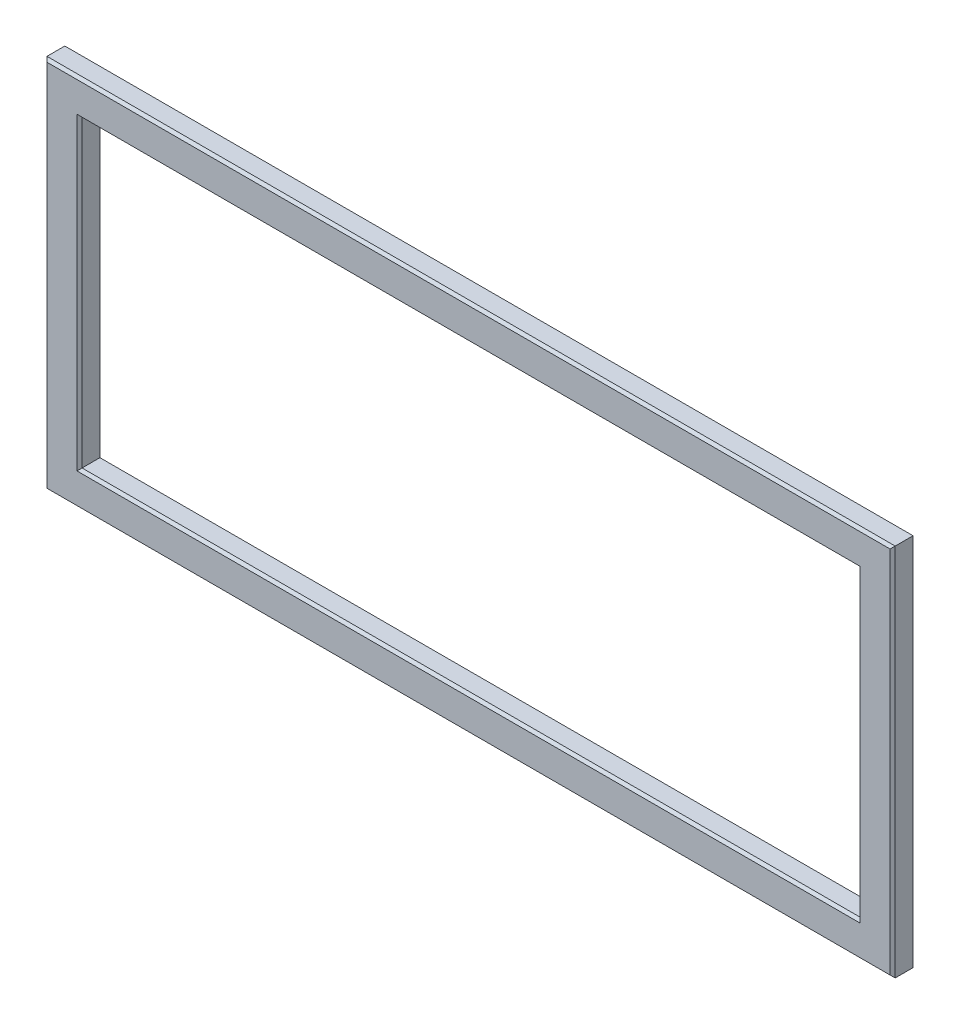
SolidWorks part; units mm, degrees
material "7075-T6 (SN)"
ref_plane "Front Plane" through (0, 0, 0) normal (0, 0, 1) x (1, 0, 0)
ref_plane "Top Plane" through (0, 0, 0) normal (0, 1, 0) x (1, 0, 0)
ref_plane "Right Plane" through (0, 0, 0) normal (1, 0, 0) x (0, 0, -1)
sketch "Sketch1" plane through (0, 0, 0) normal (0, 0, 1) x (1, 0, 0)
  line L43 (-4.2125, 142.325) -> (328.0625, 142.325)
  line L44 (-4.2125, 142.325) -> (-4.2125, -4.2125)
  line L45 (-4.2125, -4.2125) -> (328.0625, -4.2125)
  line L46 (328.0625, 142.325) -> (328.0625, -4.2125)
  line L104 (313.8, 130.5625) -> (292.3, 130.5625)
  line L105 (290.8, 132.0625) -> (290.8, 132.5625)
  line L106 (280.8, 132.5625) -> (280.8, 132.0625)
  line L107 (279.3, 130.5625) -> (168.425, 130.5625)
  line L108 (166.925, 132.0625) -> (166.925, 132.5625)
  line L109 (156.925, 132.5625) -> (156.925, 132.0625)
  line L110 (155.425, 130.5625) -> (44.55, 130.5625)
  line L111 (43.05, 132.0625) -> (43.05, 132.5625)
  line L112 (33.05, 132.5625) -> (33.05, 132.0625)
  line L113 (31.55, 130.5625) -> (10.05, 130.5625)
  line L114 (7.55, 128.0625) -> (7.55, 116.5625)
  line L115 (6.05, 115.0625) -> (5.55, 115.0625)
  line L116 (5.55, 105.0625) -> (6.05, 105.0625)
  line L117 (7.55, 103.5625) -> (7.55, 34.55)
  line L118 (6.05, 33.05) -> (5.55, 33.05)
  line L119 (5.55, 23.05) -> (6.05, 23.05)
  line L120 (7.55, 21.55) -> (7.55, 10.05)
  line L121 (10.05, 7.55) -> (31.55, 7.55)
  line L122 (33.05, 6.05) -> (33.05, 5.55)
  line L123 (43.05, 5.55) -> (43.05, 6.05)
  line L124 (44.55, 7.55) -> (155.425, 7.55)
  line L125 (156.925, 6.05) -> (156.925, 5.55)
  line L126 (166.925, 5.55) -> (166.925, 6.05)
  line L127 (168.425, 7.55) -> (279.3, 7.55)
  line L128 (280.8, 6.05) -> (280.8, 5.55)
  line L129 (290.8, 5.55) -> (290.8, 6.05)
  line L130 (292.3, 7.55) -> (313.8, 7.55)
  line L131 (316.3, 10.05) -> (316.3, 21.55)
  line L132 (317.8, 23.05) -> (318.3, 23.05)
  line L133 (318.3, 33.05) -> (317.8, 33.05)
  line L134 (316.3, 34.55) -> (316.3, 103.5625)
  line L135 (317.8, 105.0625) -> (318.3, 105.0625)
  line L136 (318.3, 115.0625) -> (317.8, 115.0625)
  line L137 (316.3, 116.5625) -> (316.3, 128.0625)
  line L138 (313.8, 130.5625) -> (292.3, 130.5625)
  line L139 (290.8, 132.0625) -> (290.8, 132.5625)
  line L140 (280.8, 132.5625) -> (280.8, 132.0625)
  line L141 (279.3, 130.5625) -> (168.425, 130.5625)
  line L142 (166.925, 132.0625) -> (166.925, 132.5625)
  line L143 (156.925, 132.5625) -> (156.925, 132.0625)
  line L144 (155.425, 130.5625) -> (44.55, 130.5625)
  line L145 (43.05, 132.0625) -> (43.05, 132.5625)
  line L146 (33.05, 132.5625) -> (33.05, 132.0625)
  line L147 (31.55, 130.5625) -> (10.05, 130.5625)
  line L148 (7.55, 128.0625) -> (7.55, 116.5625)
  line L149 (6.05, 115.0625) -> (5.55, 115.0625)
  line L150 (5.55, 105.0625) -> (6.05, 105.0625)
  line L151 (7.55, 103.5625) -> (7.55, 34.55)
  line L152 (6.05, 33.05) -> (5.55, 33.05)
  line L153 (5.55, 23.05) -> (6.05, 23.05)
  line L154 (7.55, 21.55) -> (7.55, 10.05)
  line L155 (10.05, 7.55) -> (31.55, 7.55)
  line L156 (33.05, 6.05) -> (33.05, 5.55)
  line L157 (43.05, 5.55) -> (43.05, 6.05)
  line L158 (44.55, 7.55) -> (155.425, 7.55)
  line L159 (156.925, 6.05) -> (156.925, 5.55)
  line L160 (166.925, 5.55) -> (166.925, 6.05)
  line L161 (168.425, 7.55) -> (279.3, 7.55)
  line L162 (280.8, 6.05) -> (280.8, 5.55)
  line L163 (290.8, 5.55) -> (290.8, 6.05)
  line L164 (292.3, 7.55) -> (313.8, 7.55)
  line L165 (316.3, 10.05) -> (316.3, 21.55)
  line L166 (317.8, 23.05) -> (318.3, 23.05)
  line L167 (318.3, 33.05) -> (317.8, 33.05)
  line L168 (316.3, 34.55) -> (316.3, 103.5625)
  line L169 (317.8, 105.0625) -> (318.3, 105.0625)
  line L170 (318.3, 115.0625) -> (317.8, 115.0625)
  line L171 (316.3, 116.5625) -> (316.3, 128.0625)
  arc A136 (290.8, 132.0625) -> (292.3, 130.5625) centre (292.3, 132.0625) ccw
  arc A137 (290.8, 132.5625) -> (280.8, 132.5625) centre (285.8, 132.5625) ccw
  arc A138 (279.3, 130.5625) -> (280.8, 132.0625) centre (279.3, 132.0625) ccw
  arc A139 (166.925, 132.0625) -> (168.425, 130.5625) centre (168.425, 132.0625) ccw
  arc A140 (166.925, 132.5625) -> (156.925, 132.5625) centre (161.925, 132.5625) ccw
  arc A141 (155.425, 130.5625) -> (156.925, 132.0625) centre (155.425, 132.0625) ccw
  arc A142 (43.05, 132.0625) -> (44.55, 130.5625) centre (44.55, 132.0625) ccw
  arc A143 (43.05, 132.5625) -> (33.05, 132.5625) centre (38.05, 132.5625) ccw
  arc A144 (31.55, 130.5625) -> (33.05, 132.0625) centre (31.55, 132.0625) ccw
  arc A145 (10.05, 130.5625) -> (7.55, 128.0625) centre (10.05, 128.0625) ccw
  arc A146 (6.05, 115.0625) -> (7.55, 116.5625) centre (6.05, 116.5625) ccw
  arc A147 (5.55, 115.0625) -> (5.55, 105.0625) centre (5.55, 110.0625) ccw
  arc A148 (7.55, 103.5625) -> (6.05, 105.0625) centre (6.05, 103.5625) ccw
  arc A149 (6.05, 33.05) -> (7.55, 34.55) centre (6.05, 34.55) ccw
  arc A150 (5.55, 33.05) -> (5.55, 23.05) centre (5.55, 28.05) ccw
  arc A151 (7.55, 21.55) -> (6.05, 23.05) centre (6.05, 21.55) ccw
  arc A152 (7.55, 10.05) -> (10.05, 7.55) centre (10.05, 10.05) ccw
  arc A153 (33.05, 6.05) -> (31.55, 7.55) centre (31.55, 6.05) ccw
  arc A154 (33.05, 5.55) -> (43.05, 5.55) centre (38.05, 5.55) ccw
  arc A155 (44.55, 7.55) -> (43.05, 6.05) centre (44.55, 6.05) ccw
  arc A156 (156.925, 6.05) -> (155.425, 7.55) centre (155.425, 6.05) ccw
  arc A157 (156.925, 5.55) -> (166.925, 5.55) centre (161.925, 5.55) ccw
  arc A158 (168.425, 7.55) -> (166.925, 6.05) centre (168.425, 6.05) ccw
  arc A159 (280.8, 6.05) -> (279.3, 7.55) centre (279.3, 6.05) ccw
  arc A160 (280.8, 5.55) -> (290.8, 5.55) centre (285.8, 5.55) ccw
  arc A161 (292.3, 7.55) -> (290.8, 6.05) centre (292.3, 6.05) ccw
  arc A162 (313.8, 7.55) -> (316.3, 10.05) centre (313.8, 10.05) ccw
  arc A163 (317.8, 23.05) -> (316.3, 21.55) centre (317.8, 21.55) ccw
  arc A164 (318.3, 23.05) -> (318.3, 33.05) centre (318.3, 28.05) ccw
  arc A165 (316.3, 34.55) -> (317.8, 33.05) centre (317.8, 34.55) ccw
  arc A166 (317.8, 105.0625) -> (316.3, 103.5625) centre (317.8, 103.5625) ccw
  arc A167 (318.3, 105.0625) -> (318.3, 115.0625) centre (318.3, 110.0625) ccw
  arc A168 (316.3, 116.5625) -> (317.8, 115.0625) centre (317.8, 116.5625) ccw
  arc A169 (316.3, 128.0625) -> (313.8, 130.5625) centre (313.8, 128.0625) ccw
  arc A170 (290.8, 132.0625) -> (292.3, 130.5625) centre (292.3, 132.0625) ccw
  arc A171 (290.8, 132.5625) -> (280.8, 132.5625) centre (285.8, 132.5625) ccw
  arc A172 (279.3, 130.5625) -> (280.8, 132.0625) centre (279.3, 132.0625) ccw
  arc A173 (166.925, 132.0625) -> (168.425, 130.5625) centre (168.425, 132.0625) ccw
  arc A174 (166.925, 132.5625) -> (156.925, 132.5625) centre (161.925, 132.5625) ccw
  arc A175 (155.425, 130.5625) -> (156.925, 132.0625) centre (155.425, 132.0625) ccw
  arc A176 (43.05, 132.0625) -> (44.55, 130.5625) centre (44.55, 132.0625) ccw
  arc A177 (43.05, 132.5625) -> (33.05, 132.5625) centre (38.05, 132.5625) ccw
  arc A178 (31.55, 130.5625) -> (33.05, 132.0625) centre (31.55, 132.0625) ccw
  arc A179 (10.05, 130.5625) -> (7.55, 128.0625) centre (10.05, 128.0625) ccw
  arc A180 (6.05, 115.0625) -> (7.55, 116.5625) centre (6.05, 116.5625) ccw
  arc A181 (5.55, 115.0625) -> (5.55, 105.0625) centre (5.55, 110.0625) ccw
  arc A182 (7.55, 103.5625) -> (6.05, 105.0625) centre (6.05, 103.5625) ccw
  arc A183 (6.05, 33.05) -> (7.55, 34.55) centre (6.05, 34.55) ccw
  arc A184 (5.55, 33.05) -> (5.55, 23.05) centre (5.55, 28.05) ccw
  arc A185 (7.55, 21.55) -> (6.05, 23.05) centre (6.05, 21.55) ccw
  arc A186 (7.55, 10.05) -> (10.05, 7.55) centre (10.05, 10.05) ccw
  arc A187 (33.05, 6.05) -> (31.55, 7.55) centre (31.55, 6.05) ccw
  arc A188 (33.05, 5.55) -> (43.05, 5.55) centre (38.05, 5.55) ccw
  arc A189 (44.55, 7.55) -> (43.05, 6.05) centre (44.55, 6.05) ccw
  arc A190 (156.925, 6.05) -> (155.425, 7.55) centre (155.425, 6.05) ccw
  arc A191 (156.925, 5.55) -> (166.925, 5.55) centre (161.925, 5.55) ccw
  arc A192 (168.425, 7.55) -> (166.925, 6.05) centre (168.425, 6.05) ccw
  arc A193 (280.8, 6.05) -> (279.3, 7.55) centre (279.3, 6.05) ccw
  arc A194 (280.8, 5.55) -> (290.8, 5.55) centre (285.8, 5.55) ccw
  arc A195 (292.3, 7.55) -> (290.8, 6.05) centre (292.3, 6.05) ccw
  arc A196 (313.8, 7.55) -> (316.3, 10.05) centre (313.8, 10.05) ccw
  arc A197 (317.8, 23.05) -> (316.3, 21.55) centre (317.8, 21.55) ccw
  arc A198 (318.3, 23.05) -> (318.3, 33.05) centre (318.3, 28.05) ccw
  arc A199 (316.3, 34.55) -> (317.8, 33.05) centre (317.8, 34.55) ccw
  arc A200 (317.8, 105.0625) -> (316.3, 103.5625) centre (317.8, 103.5625) ccw
  arc A201 (318.3, 105.0625) -> (318.3, 115.0625) centre (318.3, 110.0625) ccw
  arc A202 (316.3, 116.5625) -> (317.8, 115.0625) centre (317.8, 116.5625) ccw
  arc A203 (316.3, 128.0625) -> (313.8, 130.5625) centre (313.8, 128.0625) ccw
  point P0 (328.06, -21.9957)
  point P2 (0, 0)
  point P3 (0, 0)
  point P5 (0, 0)
  point P7 (0, 0)
  point P14 (7.05, 110.0625)
  point P173 (0, 0)
  point P175 (0, 0)
  point P176 (0, 0)
  dimension "D2" = 4.7625
  dimension "D3" = 4.7625
  dimension "D4" = 4.7625
  dimension "D5" = 4.7625
  dimension "D1" = 0.5
extrude "Boss-Extrude1" add sketch "Sketch1" against normal up to surface and the other way up to surface rebuild error yes
sketch "Sketch2" plane through (0, 0, 1) normal (0, 0, 1) x (1, 0, 0)
  line L28 (7.55, 128.0625) -> (7.55, 116.5625) construction
  line L30 (161.925, 142.325) -> (161.925, -4.2125) construction
  line L31 (-4.2125, 69.0562) -> (328.0625, 69.0562) construction
  line L32 (328.0625, -4.2125) -> (328.0625, 142.325) construction
  line L36 (328.0625, 142.325) -> (-4.2125, 142.325)
  line L38 (-4.2125, 142.325) -> (-4.2125, -4.2125)
  line L39 (9.55, 128.5625) -> (314.3, 128.5625)
  line L40 (-4.2125, -4.2125) -> (328.0625, -4.2125)
  line L41 (9.55, 128.5625) -> (9.55, 9.55)
  line L42 (328.0625, -4.2125) -> (328.0625, 142.325)
  line L43 (9.55, 9.55) -> (314.3, 9.55)
  line L44 (328.0625, 142.325) -> (-4.2125, 142.325)
  line L46 (-4.2125, 142.325) -> (-4.2125, -4.2125)
  line L48 (-4.2125, -4.2125) -> (328.0625, -4.2125)
  line L50 (328.0625, -4.2125) -> (328.0625, 142.325)
  line L52 (314.3, 128.5625) -> (314.3, 9.55)
  dimension "D2" = 11.7625
  dimension "D3" = 13.7625
  dimension "D4" = 13.7625
  dimension "D5" = 13.7625
  dimension "D6" = 13.7625
extrude "Boss-Extrude2" add sketch "Sketch2" along normal blind 8 contours L50 L44 L46 L48 region at (324.431, 69.0562, 1)
chamfer "Chamfer1" distance 1 angle 45 8 edges at (328.0625, 69.0562, 9) (161.925, -4.2125, 9) (-4.2125, 69.0562, 9) (161.925, 142.325, 9) (9.55, 69.0562, 9) (161.925, 9.55, 9) (314.3, 69.0562, 9) (161.925, 128.5625, 9)
hole_wizard "M2.5 Tapped Hole1" positions "Sketch3" profile "Sketch4" tap size "M2.5" standard "DIN"
sketch "Sketch3" plane through (0, 0, 1) normal (0, 0, -1) x (-1, 0, 0)
  arc A1 (-290.8, 5.55) -> (-280.8, 5.55) centre (-285.8, 5.55) ccw construction
  point P37 (-285.8, 132.5625)
  point P40 (-318.3, 110.0625)
  point P43 (-318.3, 28.05)
  point P46 (-285.8, 5.55)
  point P49 (-161.925, 5.55)
  point P52 (-38.05, 5.55)
  point P55 (-5.55, 28.05)
  point P58 (-38.05, 132.5625)
  point P61 (-5.55, 110.0625)
  point P65 (-161.925, 132.5625)
  point P69 (0, 0)
  point P70 (0, 0)
sketch "Sketch4" plane through (285.8, 132.5625, 1) normal (1, 0, 0) x (0, 1, 0)
  line L0 (0, 0) -> (0, 6.9659)
  line L1 (0, 6.9659) -> (1.025, 6.35)
  line L2 (1.025, 6.35) -> (1.025, 0)
  line L5 (1.025, 0) -> (0, 0)
  line L10 (0, 6.9659) -> (-1.025, 6.35) construction
  line L11 (0, -6.35) -> (0, 107.95) construction
  dimension "Tap Drill Dia." = 2.05
  dimension "Tap Drill Depth" = 6.35
  dimension "Drill Angle" = 118
cosmetic thread "Hole Thread2"
cosmetic thread "Hole Thread3"
cosmetic thread "Hole Thread4"
cosmetic thread "Hole Thread5"
cosmetic thread "Hole Thread6"
cosmetic thread "Hole Thread7"
cosmetic thread "Hole Thread8"
cosmetic thread "Hole Thread9"
cosmetic thread "Hole Thread10"
cosmetic thread "Hole Thread11"
equation "\"D2@Sketch1\"=\"D3@Sketch1\""
equation "\"D4@Sketch1\"=\"D3@Sketch1\""
equation "\"D5@Sketch1\"=\"D3@Sketch1\""
equation "\"D3@Sketch2\"=\"D2@Sketch2\"+2"
equation "\"D4@Sketch2\"=\"D3@Sketch2\""
equation "\"D5@Sketch2\"=\"D3@Sketch2\""
equation "\"D6@Sketch2\"=\"D3@Sketch2\""
